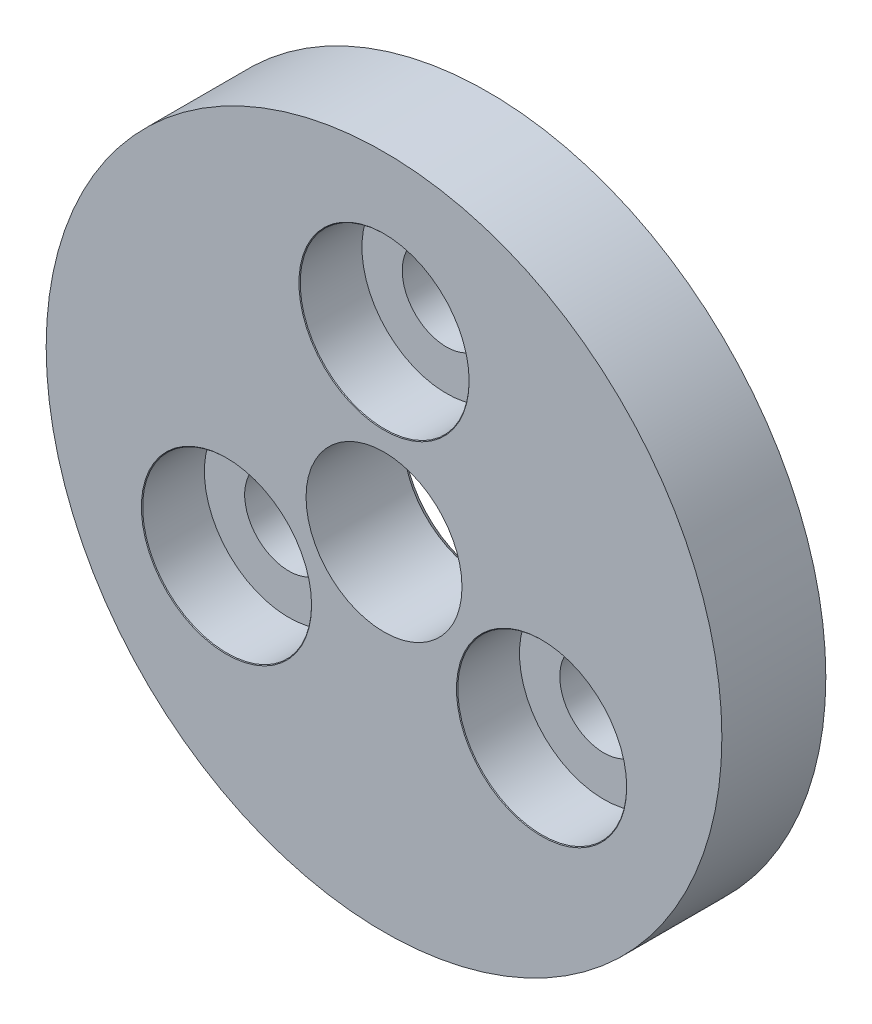
SolidWorks part; units mm, degrees
material "6061-T6 (SS)"
ref_plane "Front Plane" through (0, 0, 0) normal (0, 0, 1) x (1, 0, 0)
ref_plane "Top Plane" through (0, 0, 0) normal (0, 1, 0) x (1, 0, 0)
ref_plane "Right Plane" through (0, 0, 0) normal (1, 0, 0) x (0, 0, -1)
sketch "Sketch1" plane through (0, 0, 0) normal (0, 0, 1) x (1, 0, 0)
  circle A0 centre (0, 0) radius 13
  dimension "D1" = 26
extrude "Boss-Extrude1" add sketch "Sketch1" along normal blind 4
sketch "Sketch3" plane through (0, 0, 0) normal (0, 0, -1) x (-1, 0, 0)
  point P0 (0, 0)
hole_wizard "Ø6.0mm Dowel Hole1" positions "Sketch3" profile "Sketch4" hole size "Ø6.0" standard "DIN"
sketch "Sketch4" plane through (0, 0, 0) normal (1, 0, 0) x (0, 1, 0)
  line L0 (0, 0) -> (0, 13.8026)
  line L1 (0, 13.8026) -> (3, 12)
  line L2 (3, 12) -> (3, 0.25)
  line L3 (3, 0.25) -> (3.25, 0)
  line L5 (3.25, 0) -> (0, 0)
  line L6 (-3, 0.25) -> (-3.25, 0) construction
  line L10 (0, 13.8026) -> (-3, 12) construction
  line L11 (0, -6.35) -> (0, 107.95) construction
  dimension "Hole Dia." = 6
  dimension "Hole Depth" = 12
  dimension "Near C'Sink Dia." = 6.5
  dimension "Near C'Sink Angle" = 90
  dimension "Drill Angle" = 118
sketch "Sketch5" plane through (0, 0, 4) normal (0, 0, 1) x (1, 0, 0)
  circle A0 centre (0, 0) radius 7
  point P4 (0, 7)
  point P11 (6.0622, -3.5)
  point P12 (-6.0622, -3.5)
  dimension "D1" = 14
  dimension "D2" = 3
hole_wizard "CBORE for M3 Hex Socket Thin Head Cap Screw1" positions "Sketch5" profile "Sketch7" counterbore size "M3" standard "DIN"
sketch "Sketch7" plane through (-6.0622, -3.5, 4) normal (1, 0, 0) x (0, -1, 0)
  line L0 (0, 0) -> (0, 13.0215)
  line L1 (0, 13.0215) -> (1.7, 12)
  line L2 (1.7, 12) -> (1.7, 2.4)
  line L3 (1.7, 2.4) -> (3.25, 2.4)
  line L5 (3.25, 2.4) -> (3.25, 0.025)
  line L6 (3.25, 0.025) -> (3.275, 0)
  line L7 (3.275, 0) -> (0, 0)
  line L8 (-3.25, 0.025) -> (-3.275, 0) construction
  line L10 (0, 13.0215) -> (-1.7, 12) construction
  line L11 (0, -6.35) -> (0, 107.95) construction
  dimension "Hole Dia." = 3.4
  dimension "Hole Depth" = 12
  dimension "C'Bore Dia." = 6.5
  dimension "C'Bore Depth" = 2.4
  dimension "Near C'Sink Dia." = 6.55
  dimension "Near C'Sink Angle" = 90
  dimension "Drill Angle" = 118
